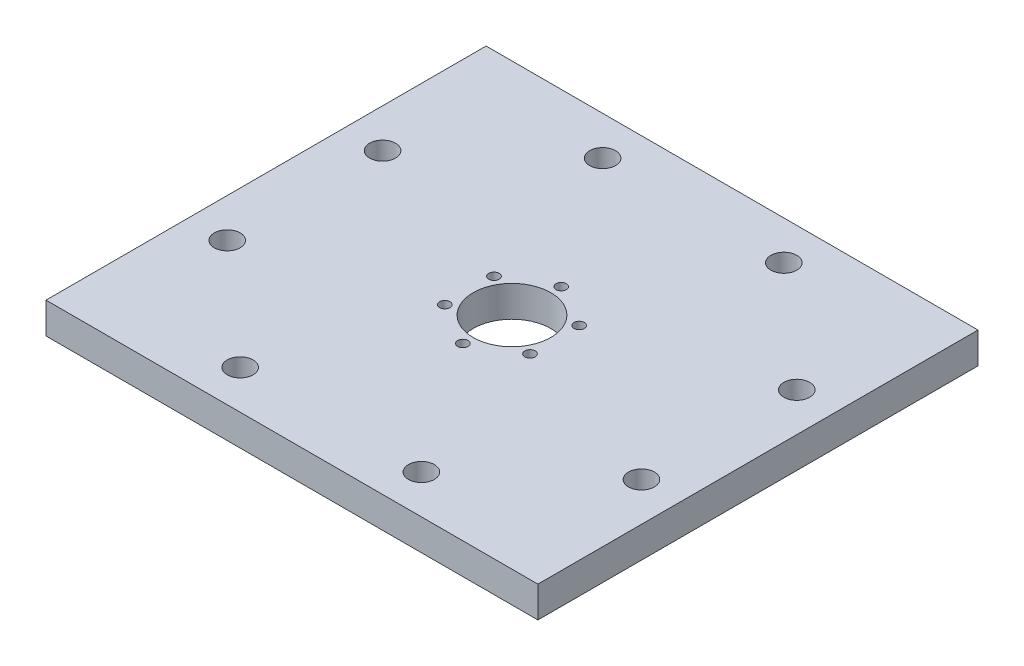
SolidWorks part; units mm, degrees
ref_plane "Front Plane" through (0, 0, 0) normal (0, 0, 1) x (1, 0, 0)
ref_plane "Top Plane" through (0, 0, 0) normal (0, 1, 0) x (1, 0, 0)
ref_plane "Right Plane" through (0, 0, 0) normal (1, 0, 0) x (0, 0, -1)
sketch "Sketch1" plane through (0, 0, 0) normal (0, 1, 0) x (1, 0, 0)
  line L0 (0, -3.3) -> (0, 3.3) construction
  line L1 (-47.5, 42.5) -> (47.5, 42.5)
  line L2 (-47.5, 42.5) -> (-47.5, -42.5)
  line L3 (-47.5, -42.5) -> (47.5, -42.5)
  line L4 (47.5, 42.5) -> (47.5, -42.5)
  line L5 (-47.5, 42.5) -> (47.5, -42.5) construction
  line L6 (-47.5, -42.5) -> (47.5, 42.5) construction
  line L7 (-3.3, 0) -> (3.3, 0) construction
  circle A0 centre (0, 0) radius 9.5 construction
  circle A1 centre (0, 9.5) radius 1
  circle A2 centre (8.2272, 4.75) radius 1
  circle A3 centre (8.2272, -4.75) radius 1
  circle A4 centre (0, -9.5) radius 1
  circle A5 centre (-8.2272, -4.75) radius 1
  circle A6 centre (-8.2272, 4.75) radius 1
  circle A7 centre (0, 0) radius 7.5
  circle A8 centre (-17.5, 35) radius 2.5
  circle A9 centre (17.5, 35) radius 2.5
  circle A10 centre (17.5, -35) radius 2.5
  circle A11 centre (-17.5, -35) radius 2.5
  circle A12 centre (-40, 15) radius 2.5
  circle A13 centre (-40, -15) radius 2.5
  circle A14 centre (40, -15) radius 2.5
  circle A15 centre (40, 15) radius 2.5
  dimension "D1" = 19
  dimension "D2" = 2
  dimension "D4" = 15
  dimension "D7" = 5
  dimension "D10" = 5
  dimension "D5" = 17.5
  dimension "D6" = 95
  dimension "D8" = 85
  dimension "D9" = 35
  dimension "D11" = 40
  dimension "D12" = 15
  dimension "D3" = 6
extrude "Boss-Extrude1" add sketch "Sketch1" along normal blind 6
sketch "Sketch2" plane through (0, 0, 0) normal (0, 1, 0) x (1, 0, 0)
  line L0 (-3.3, 0) -> (3.3, 0) construction
  line L1 (0, -3.3) -> (0, 3.3) construction
  circle A0 centre (-17.5, 35) radius 6
  circle A1 centre (-17.5, -35) radius 6
  circle A2 centre (17.5, -35) radius 6
  circle A3 centre (17.5, 35) radius 6
  dimension "D1" = 12
extrude "Cut-Extrude2" cut sketch "Sketch2" along normal blind 1.5
equation "\"testbed_height\" = 91.50mm"
equation "\"plate_thickness\" = 6mm"
equation "\"main_body_splay_length\" = 48.5mm"
equation "\"splay_shaft_length_no_wires\" = 10mm"
equation "\"splay_shaft_length_wires\" = 6.5mm"
equation "\"timing_pulley_offset\" = 0mm"
equation "\"effective_motor_length\" = \"timing_pulley_offset\" + \"splay_shaft_length_no_wires\" + \"main_body_splay_length\""
equation "\"80_20_side\" = 25.4mm"
equation "\"80_20_length\" = 152.4mm"
equation "\"80_20_optic_mount_length\" = \"80_20_length\" - 25.4mm"
equation "\"optic_board_hole_size\" = 6.35mm"
equation "\"total_mounting_length\" = \"testbed_height\" - \"effective_motor_length\" - \"80_20_side\""
equation "\"mounting_vertical_portion_height\" = \"total_mounting_length\" - 2 * \"plate_thickness\""
equation "\"face_mount_width\" = 15.25mm"
equation "\"center_dist_to_face_mount_vertical_screws\" = 5mm"
equation "\"D1@Boss-Extrude1\"=\"plate_thickness\""
